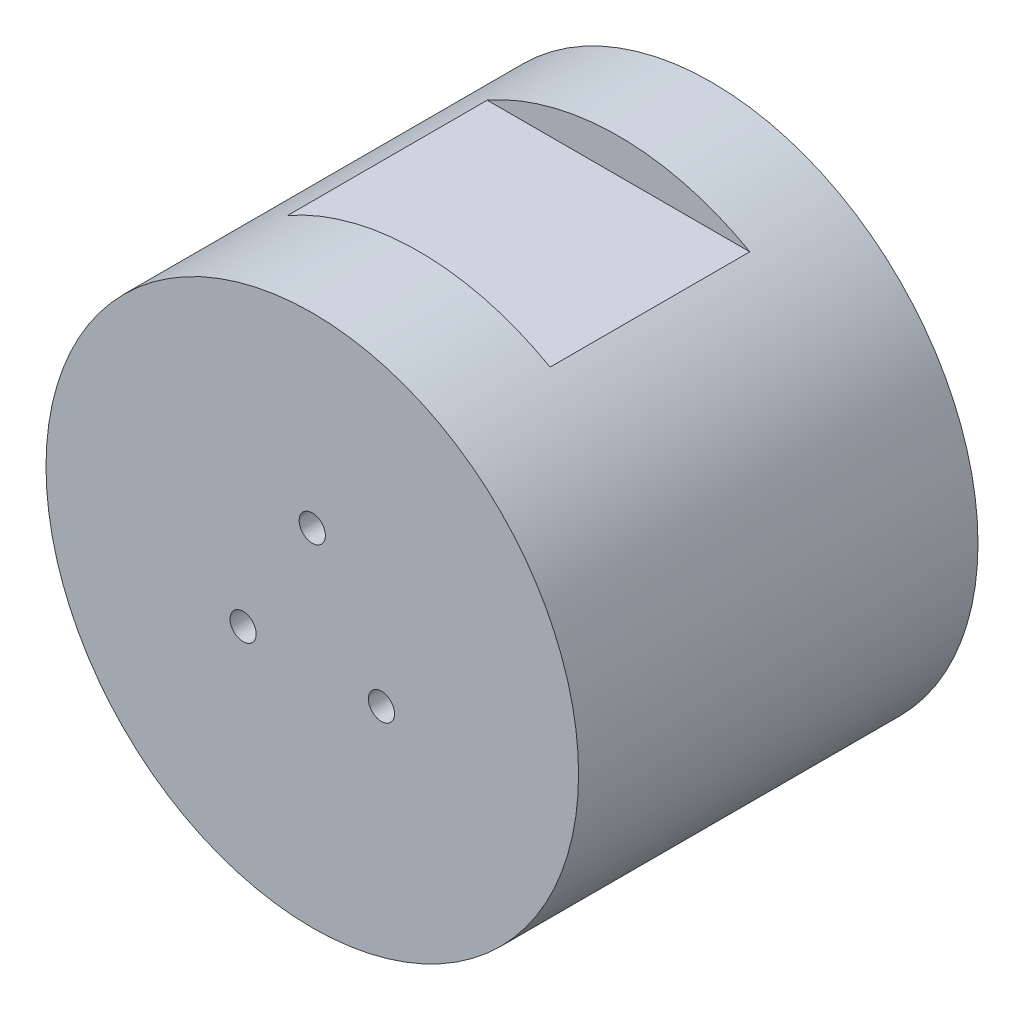
SolidWorks part; units mm, degrees
ref_plane "Front Plane" through (0, 0, 0) normal (0, 0, 1) x (1, 0, 0)
ref_plane "Top Plane" through (0, 0, 0) normal (0, 1, 0) x (1, 0, 0)
ref_plane "Right Plane" through (0, 0, 0) normal (1, 0, 0) x (0, 0, -1)
sketch "Sketch1" plane through (0, 0, 0) normal (0, 0, 1) x (1, 0, 0)
  circle A0 centre (0, 0) radius 25.4
  dimension "D1" = 50.8
extrude "Boss-Extrude1" add sketch "Sketch1" along normal blind 38.1
sketch "Sketch2" plane through (0, 0, 0) normal (0, 0, -1) x (-1, 0, 0)
  circle A0 centre (0, 0) radius 17.6759
  dimension "D1" = 35.3517
extrude "Cut-Extrude1" cut sketch "Sketch2" against normal blind 31.75
thread "Thread1" pitch 2.1167 method cut profile "Thread Profile1" start angle 0, offset 2.54, length 30.48, pitch 2.1167, diameter 35.3517
ref_plane "Plane1" through (17.6759, 0, -2.54) normal (0, -1, 0) x (1, 0, 0)
sketch "Thread Profile1" plane through (17.6759, 0, -2.54) normal (0, -1, 0) x (1, 0, 0)
  line L0 (0, 0) -> (0, 2.1167) construction
  line L1 (0, 0) -> (1.1457, 0.6615)
  line L2 (1.1457, 0.6615) -> (1.1457, 0.926)
  line L3 (1.1457, 0.926) -> (0, 1.5875)
  line L4 (1.1457, 0.7937) -> (0, 0.7937) construction
  line L11 (0, 0) -> (0, 1.5875)
  point P2 (0, 0)
  dimension "Pitch" = 2.1167
  dimension "Profile_Angle" = 60
  dimension "Profile_Land" = 0.2646
  dimension "Profile_Height" = 1.1457
sketch "Sketch6" plane through (0, 0, 0) normal (1, 0, 0) x (0, 0, -1)
  line L0 (0, 25.4) -> (-38.1, 25.4) construction
  line L1 (-8.89, 25.4) -> (-27.94, 25.4)
  line L2 (-8.89, 25.4) -> (-8.89, 22.098)
  line L3 (-8.89, 22.098) -> (-27.94, 22.098)
  line L4 (-27.94, 25.4) -> (-27.94, 22.098)
  line L5 (-8.89, 25.4) -> (-27.94, 22.098) construction
  line L6 (-8.89, 22.098) -> (-27.94, 25.4) construction
  line L7 (-38.1, -25.4) -> (0, -25.4) construction
  line L8 (-8.89, -25.4) -> (-27.94, -25.4)
  line L9 (-8.89, -25.4) -> (-8.89, -22.098)
  line L10 (-8.89, -22.098) -> (-27.94, -22.098)
  line L11 (-27.94, -25.4) -> (-27.94, -22.098)
  line L12 (-8.89, -25.4) -> (-27.94, -22.098) construction
  line L13 (-8.89, -22.098) -> (-27.94, -25.4) construction
  line L14 (0, -25.4) -> (0, 25.4) construction
  point P4 (-18.415, 23.749)
  point P11 (-18.415, -23.749)
  dimension "D1" = 44.196
  dimension "D2" = 8.89
  dimension "D3" = 19.05
extrude "Cut-Extrude3" cut sketch "Sketch6" against normal up to next and the other way up to next
sketch "Sketch7" plane through (0, 0, 31.75) normal (0, 0, -1) x (-1, 0, 0)
  circle A0 centre (0, 0) radius 12.7 construction
  circle A1 centre (0, 0) radius 7.62 construction
  circle A2 centre (0, 7.62) radius 1.25
  circle A3 centre (6.5991, -3.81) radius 1.25
  circle A4 centre (-6.5991, -3.81) radius 1.25
  point P12 (0, 0)
  dimension "D1" = 25.4
  dimension "D2" = 15.24
  dimension "D3" = 2.5
  dimension "D4" = 3
extrude "Cut-Extrude4" cut sketch "Sketch7" against normal up to next
